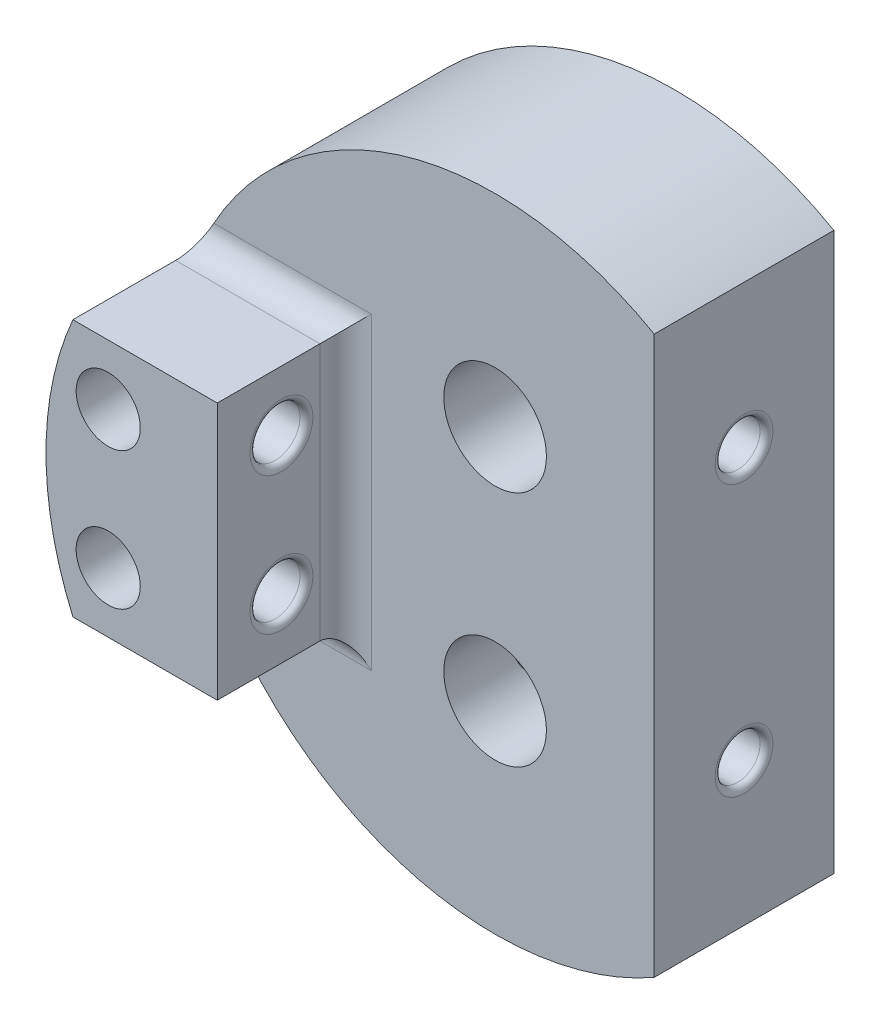
SolidWorks part; units mm, degrees
ref_plane "Front Plane" through (0, 0, 0) normal (1, 0, 0) x (0, 1, 0)
ref_plane "Top Plane" through (0, 0, 0) normal (0, 0, 1) x (0, 1, 0)
ref_plane "Right Plane" through (0, 0, 0) normal (0, 1, 0) x (-1, 0, 0)
sketch "Sketch1" plane through (0, 0, 0) normal (0, 0, 1) x (0, 1, 0)
  line L0 (-23.5, 8.5294) -> (23.5, 8.5294) construction
  line L1 (0, 25) -> (0, -25) construction
  circle A0 centre (0, 0) radius 25
  dimension "D1" = 50
extrude "Boss-Extrude1" add sketch "Sketch1" along normal blind 14
sketch "Sketch2" plane through (0, 0, 14) normal (0, 0, 1) x (0, -1, 0)
  line L0 (0, -25) -> (0, 25) construction
  line L1 (-23.5, -8.5294) -> (23.5, -8.5294)
  arc A0 (-23.5, -8.5294) -> (23.5, -8.5294) centre (0, 0) ccw
extrude "Boss-Extrude2" add sketch "Sketch2" along normal blind 10
sketch "Sketch3" plane through (0, 0, 24) normal (0, 0, 1) x (1, 0, 0)
  line L0 (-20.1507, 0) -> (-20.1507, -2.85) construction
  line L1 (-25, 0) -> (25, 0) construction
  line L2 (-8.5294, 0) -> (-25, 0) construction
  line L3 (-8.5294, -23.5) -> (-8.5294, 23.5) construction
  circle A1 centre (-20.1507, -5.35) radius 2.5
  circle A2 centre (-20.1507, 5.35) radius 2.5
  dimension "D1" = 2.85
extrude "Cut-Extrude1" cut sketch "Sketch3" against normal through all
sketch "Sketch4" plane through (0, 0, 14) normal (0, 0, 1) x (1, 0, 0)
  line L0 (0, -25) -> (0, 25) construction
  line L1 (25, 0) -> (-25, 0) construction
  line L2 (0, 0) -> (0, -5.25) construction
  line L3 (0, -5.25) -> (0, 0)
  circle A0 centre (0, 0) radius 25 construction
  circle A1 centre (0, -9.25) radius 4
  circle A2 centre (0, 9.25) radius 4
  dimension "D1" = 8
extrude "Cut-Extrude2" cut sketch "Sketch4" against normal through all contours A2 | A1 region at (0, -9.25, 14) region at (0, 9.25, 14)
sketch "Sketch5" plane through (-8.5294, 0, 0) normal (1, 0, 0) x (0, 1, 0)
  line L0 (-23.5, 19) -> (23.5, 19) construction
  line L1 (-23.5, 24) -> (-23.5, 14) construction
  line L2 (23.5, 24) -> (23.5, 14) construction
  line L3 (0, 24) -> (0, 14) construction
  line L4 (-23.5, 24) -> (23.5, 24) construction
  line L5 (25, 14) -> (-25, 14) construction
  line L6 (-7.85, 24) -> (-2.85, 24) construction
  line L7 (-13.25, 7) -> (-7.85, 7) construction
  line L8 (-13.25, 14) -> (-13.25, 0) construction
  line L9 (-7.85, 24) -> (-7.85, 0) construction
  circle A0 centre (-5.35, 19) radius 1.95
  circle A1 centre (5.35, 19) radius 1.95
  circle A2 centre (-10.55, 7) radius 1.75
  circle A3 centre (10.55, 7) radius 1.75
  dimension "D1" = 3.9
extrude "M3 Hole for heatset" cut sketch "Sketch5" against normal through all both and the other way through all contours A0 | A1 | A2 | A3 | A0 | A1 | A2 | A3 region at (-8.5294, -5.35, 19) region at (-8.5294, 5.35, 19) region at (-8.5294, -10.55, 7) region at (-8.5294, 10.55, 7)
sketch "Sketch7" plane through (0, 0, 24) normal (0, 0, 1) x (1, 0, 0)
  line L0 (-22.8997, 10.0301) -> (-11.6507, 10.0301)
  line L1 (-8.5294, -23.5) -> (-8.5294, 23.5) construction
  line L2 (-8.5294, 10.0301) -> (-8.5294, 23.5)
  line L3 (-25, 0) -> (-8.5294, 0) construction
  line L4 (-8.5294, -10.0301) -> (-8.5294, -23.5)
  line L5 (-22.8997, -10.0301) -> (-11.6507, -10.0301)
  line L6 (-8.5294, 10.0301) -> (-8.5294, -10.0301)
  line L7 (-17.6507, -5.35) -> (-11.6507, -5.35) construction
  line L8 (-11.6507, 10.0301) -> (-11.6507, -10.0301)
  arc A0 (-22.8997, 10.0301) -> (-8.6579, 23.453) centre (0, 0) cw
  arc A1 (-22.8997, -10.0301) -> (-8.6579, -23.453) centre (0, 0) ccw
  circle A2 centre (-20.1507, -5.35) radius 2.5 construction
  arc M4 (-8.5294, 23.5) -> (-8.5294, -23.5) centre (0, 0) ccw
  line M5 (-8.5294, -23.5) -> (-8.5294, 23.5)
  dimension "D1" = 6
extrude "Cut-Extrude5" cut sketch "Sketch7" against normal blind 10 contours L0 L8 L5 M4 M5 region at (-16.8097, 17.8354, 24)
sketch "Sketch8" plane through (0, 0, 14) normal (0, 0, 1) x (1, 0, 0)
  line L0 (-4, 9.25) -> (4, 9.25)
  line L1 (4, 24.6779) -> (4, -24.6779) construction
  circle A0 centre (0, 9.25) radius 4 construction
  circle A1 centre (0, 0) radius 25 construction
  dimension "D1" = 8
ref_plane "Plane1" through (4, 0, 0) normal (-1, 0, 0) x (0, -1, 0)
sketch "Sketch9" plane through (4, 0, 0) normal (-1, 0, 0) x (0, -1, 0)
  line L1 (-25.9824, 15.6208) -> (26.3443, 15.6208)
  line L2 (-25.9824, 15.6208) -> (-25.9824, -2.6899)
  line L3 (-25.9824, -2.6899) -> (26.3443, -2.6899)
  line L4 (26.3443, 15.6208) -> (26.3443, -2.6899)
  line L5 (-25.9824, 15.6208) -> (26.3443, -2.6899) construction
  line L6 (-25.9824, -2.6899) -> (26.3443, 15.6208) construction
  point P4 (0.1809, 6.4654)
extrude "Cut-Extrude6" cut sketch "Sketch9" against normal blind 21 from offset 8.4 offset against normal yes
sketch "Sketch10" plane through (0, 0, 14) normal (0, 0, 1) x (1, 0, 0)
  line L0 (-4.85, -10.1) -> (-4.85, 10.1)
  line L1 (0, 0) -> (12.414, 0) construction
  line L2 (-15.1, -10.1) -> (-15.1, 10.1)
  line L4 (-15.1, 0) -> (-4.85, 0)
  line L7 (0, -25) -> (0, 25) construction
  line L9 (4, -9.25) -> (4.5, -9.25)
  line L10 (4, 24.6779) -> (4, -24.6779) construction
  line L11 (-25, 0) -> (25, 0) construction
  circle A0 centre (5.099, -18.02) radius 4.1
  arc A1 (-15.1, -10.1) -> (-4.85, -10.1) centre (-9.975, -10.1) ccw
  arc A4 (-15.1, 10.1) -> (-4.85, 10.1) centre (-9.975, 10.1) cw
  circle A5 centre (0, 0) radius 25 construction
  circle A6 centre (0, -9.25) radius 4 construction
  circle A8 centre (6.207, 0) radius 4.1
  circle A9 centre (5.099, 18.02) radius 4.1
  line M26 (-22.8997, 10.0301) -> (-11.6507, 10.0301)
  line M27 (-11.6507, 10.0301) -> (-11.6507, -10.0301)
  line M28 (-11.6507, -10.0301) -> (-22.8997, -10.0301)
  dimension "D2" = 10.25
  dimension "D1" = 8.2
  dimension "D3" = 8.2
extrude "Magnet Slots" cut sketch "Sketch10" along direction (0, 0, 1) on the side of the normal blind 4 from offset 13.8 contours L2 A1 L0 L4 M27 M28 | A0 | A8 | A9 | A4 L2 L4 L0 M26 M27 | L2 L4 M27 M26 | L4 L2 M28 M27 region at (-8.9073, -7.7663, 14) region at (-8.9073, 7.7663, 14) region at (-13.3753, -5.0151, 14) region at (-13.3753, 5.0151, 14) region at (5.099, -18.02, 14) region at (6.207, 0, 14) region at (5.099, 18.02, 14) offset against normal yes
fillet "Fillet1" radius 2 3 edges at (-17.2752, 10.0301, 14) (-11.6507, 0, 14) (-17.2752, -10.0301, 14)
fillet "Fillet2" radius 0.5 4 edges at (-11.6507, -5.35, 20.95) (-11.6507, 5.35, 20.95) (12.4, 10.55, 8.75) (12.4, -10.55, 8.75)
